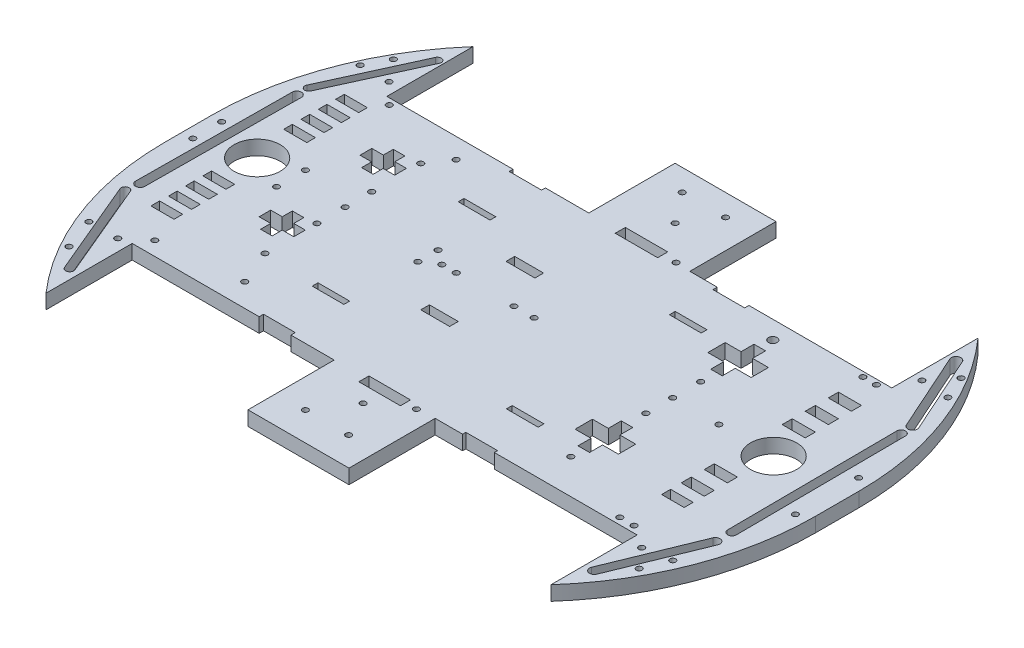
SolidWorks part; units mm, degrees
ref_plane "Front Plane" through (0, 0, 0) normal (0, 0, 1) x (1, 0, 0)
ref_plane "Top Plane" through (0, 0, 0) normal (0, 1, 0) x (1, 0, 0)
ref_plane "Right Plane" through (0, 0, 0) normal (1, 0, 0) x (0, 0, -1)
sketch "Sketch1" plane through (0, 0, 0) normal (0, 1, 0) x (1, 0, 0)
  line L1 (50.2895, -119.8741) -> (-174.7105, -119.8741)
  line L2 (50.2895, -119.8741) -> (50.2895, 28.1259)
  line L3 (50.2895, 28.1259) -> (-174.7105, 28.1259)
  line L4 (-174.7105, -119.8741) -> (-174.7105, 28.1259)
  line L5 (50.2895, -119.8741) -> (-174.7105, 28.1259) construction
  line L6 (50.2895, 28.1259) -> (-174.7105, -119.8741) construction
  point P0 (-62.2105, -45.8741)
extrude "Boss-Extrude1" add sketch "Sketch1" along normal blind 5
sketch "Sketch2" plane through (0, 5, 0) normal (0, 1, 0) x (1, 0, 0)
  line L1 (-150, 28.25) -> (-80, 28.25)
  line L2 (-150, 28.25) -> (-150, -1.75)
  line L3 (-150, -1.75) -> (-80, -1.75)
  line L4 (-80, 28.25) -> (-80, -1.75)
  line L5 (-150, 28.25) -> (-80, -1.75) construction
  line L6 (-150, -1.75) -> (-80, 28.25) construction
  line L7 (-45, 28.25) -> (25, 28.25)
  line L8 (-45, 28.25) -> (-45, -1.75)
  line L9 (-45, -1.75) -> (25, -1.75)
  line L10 (25, 28.25) -> (25, -1.75)
  line L11 (-45, 28.25) -> (25, -1.75) construction
  line L12 (-45, -1.75) -> (25, 28.25) construction
  line L13 (-150, -90) -> (-80, -90)
  line L14 (-150, -90) -> (-150, -120)
  line L15 (-150, -120) -> (-80, -120)
  line L16 (-80, -90) -> (-80, -120)
  line L17 (-150, -90) -> (-80, -120) construction
  line L18 (-150, -120) -> (-80, -90) construction
  line L19 (-45, -90) -> (25, -90)
  line L20 (-45, -90) -> (-45, -120)
  line L21 (-45, -120) -> (25, -120)
  line L22 (25, -90) -> (25, -120)
  line L23 (-45, -90) -> (25, -120) construction
  line L24 (-45, -120) -> (25, -90) construction
  point P0 (-115, 13.25)
  point P5 (-10, 13.25)
  point P10 (-10, -105)
  point P11 (-115, -105)
  point P20 (0, 0)
  point P21 (0, 0)
  point P22 (0, 0)
  point P23 (0, 0)
  point P24 (0, 0)
  point P25 (0, 0)
  point P26 (0, 0)
  point P27 (0, 0)
  point P28 (0, 0)
  point P29 (0, 0)
  point P30 (0, 0)
  point P31 (0, 0)
  point P32 (0, 0)
extrude "Cut-Extrude4" cut sketch "Sketch2" against normal blind 5
fillet "Fillet3" radius 100 1 edges at (50.2895, 2.5, -28.1259)
fillet "Fillet4" radius 100 1 edges at (50.2895, 2.5, 119.8741)
fillet "Fillet5" radius 100 1 edges at (-174.7105, 2.5, 119.8741)
fillet "Fillet6" radius 100 1 edges at (-174.7105, 2.5, -28.1259)
sketch "Sketch3" plane through (0, 5, 0) normal (0, 1, 0) x (1, 0, 0)
  line L0 (40.2781, -13.7848) -> (40.6645, -72.7835) construction
  line L1 (41.7887, -13.7749) -> (42.1752, -72.7736)
  line L2 (38.7674, -13.7947) -> (39.1539, -72.7934)
  line L3 (40.4626, -78.3743) -> (28.2879, -108.1748) construction
  line L4 (41.9597, -78.986) -> (29.785, -108.7865)
  line L5 (38.9654, -77.7627) -> (26.7907, -107.5632)
  line L6 (40.1409, -9.6854) -> (27.8591, 17.6854) construction
  line L7 (38.6468, -10.3558) -> (26.365, 17.0149)
  line L8 (41.635, -9.0149) -> (29.3532, 18.3558)
  arc A0 (41.7887, -13.7749) -> (38.7674, -13.7947) centre (40.2781, -13.7848) ccw
  arc A1 (39.1539, -72.7934) -> (42.1752, -72.7736) centre (40.6645, -72.7835) ccw
  arc A2 (41.9597, -78.986) -> (38.9654, -77.7627) centre (40.4626, -78.3743) ccw
  arc A3 (26.7907, -107.5632) -> (29.785, -108.7865) centre (28.2879, -108.1748) ccw
  arc A4 (38.6468, -10.3558) -> (41.635, -9.0149) centre (40.1409, -9.6854) ccw
  arc A5 (29.3532, 18.3558) -> (26.365, 17.0149) centre (27.8591, 17.6854) ccw
  point P2 (40.4713, -43.2842)
  point P7 (34.3752, -93.2746)
  point P14 (34, 4)
extrude "Cut-Extrude5" cut sketch "Sketch3" against normal blind 5
sketch "Sketch4" plane through (0, 5, 0) normal (0, 1, 0) x (1, 0, 0)
  circle A0 centre (46.243, -34.4925) radius 1
  circle A1 centre (46.243, -56.4082) radius 1
extrude "Cut-Extrude6" cut sketch "Sketch4" against normal blind 5
sketch "Sketch5" plane through (0, 5, 0) normal (0, 1, 0) x (1, 0, 0)
  circle A0 centre (16.7247, -87.7343) radius 1
  circle A1 centre (21.6512, -87.7207) radius 1
  circle A2 centre (29.6052, -93.0384) radius 1
  circle A3 centre (35.4425, -99.7319) radius 1
  circle A4 centre (38.8294, -91.479) radius 1
  circle A5 centre (27.9671, 5.7106) radius 1
  circle A6 centre (34.048, 13.2015) radius 1
  circle A7 centre (37.5731, 5.0937) radius 1
  circle A8 centre (16.7037, -3.4746) radius 1
  circle A9 centre (21.3826, -3.4853) radius 1
  point P20 (0, 0)
  point P21 (16.7247, -87.7343)
  point P22 (0, 0)
  point P23 (0, 0)
  point P24 (0, 0)
  point P25 (0, 0)
  point P26 (35.4425, -99.7319)
  point P27 (0, 0)
  point P28 (29.6052, -93.0384)
extrude "Cut-Extrude7" cut sketch "Sketch5" against normal blind 5
sketch "Sketch6" plane through (0, 5, 0) normal (0, 1, 0) x (1, 0, 0)
  line L0 (-166.5243, -70.7082) -> (-166.0912, -16.8551) construction
  line L1 (17, -12.25) -> (25, -12.25)
  line L2 (17, -12.25) -> (17, -15.75)
  line L3 (17, -15.75) -> (25, -15.75)
  line L4 (25, -12.25) -> (25, -15.75)
  line L5 (17, -12.25) -> (25, -15.75) construction
  line L6 (17, -15.75) -> (25, -12.25) construction
  line L7 (17, -20.25) -> (25, -20.25)
  line L8 (17, -20.25) -> (17, -23.75)
  line L9 (17, -23.75) -> (25, -23.75)
  line L10 (25, -20.25) -> (25, -23.75)
  line L11 (17, -20.25) -> (25, -23.75) construction
  line L12 (17, -23.75) -> (25, -20.25) construction
  line L13 (25, -31.75) -> (17, -31.75)
  line L14 (25, -31.75) -> (25, -28.25)
  line L15 (25, -28.25) -> (17, -28.25)
  line L16 (17, -31.75) -> (17, -28.25)
  line L17 (25, -31.75) -> (17, -28.25) construction
  line L18 (25, -28.25) -> (17, -31.75) construction
  line L19 (25, -74.75) -> (17, -74.75)
  line L20 (25, -74.75) -> (25, -71.25)
  line L21 (25, -71.25) -> (17, -71.25)
  line L22 (17, -74.75) -> (17, -71.25)
  line L23 (25, -74.75) -> (17, -71.25) construction
  line L24 (25, -71.25) -> (17, -74.75) construction
  line L25 (25, -66.75) -> (17, -66.75)
  line L26 (25, -66.75) -> (25, -63.25)
  line L27 (25, -63.25) -> (17, -63.25)
  line L28 (17, -66.75) -> (17, -63.25)
  line L29 (25, -66.75) -> (17, -63.25) construction
  line L30 (25, -63.25) -> (17, -66.75) construction
  line L31 (25, -58.75) -> (17, -58.75)
  line L32 (25, -58.75) -> (25, -55.25)
  line L33 (25, -55.25) -> (17, -55.25)
  line L34 (17, -58.75) -> (17, -55.25)
  line L35 (25, -58.75) -> (17, -55.25) construction
  line L36 (25, -55.25) -> (17, -58.75) construction
  line L37 (-17.5, -17) -> (-2.5, -17)
  line L38 (-17.5, -17) -> (-17.5, -23)
  line L39 (-17.5, -23) -> (-2.5, -23)
  line L40 (-2.5, -17) -> (-2.5, -23)
  line L41 (-17.5, -17) -> (-2.5, -23) construction
  line L42 (-17.5, -23) -> (-2.5, -17) construction
  line L43 (-12, -12.5) -> (-8, -12.5)
  line L44 (-12, -12.5) -> (-12, -27.5)
  line L45 (-12, -27.5) -> (-8, -27.5)
  line L46 (-8, -12.5) -> (-8, -27.5)
  line L47 (-12, -12.5) -> (-8, -27.5) construction
  line L48 (-12, -27.5) -> (-8, -12.5) construction
  line L49 (-2.5, -63) -> (-17.5, -63)
  line L50 (-2.5, -63) -> (-2.5, -69)
  line L51 (-2.5, -69) -> (-17.5, -69)
  line L52 (-17.5, -63) -> (-17.5, -69)
  line L53 (-2.5, -63) -> (-17.5, -69) construction
  line L54 (-2.5, -69) -> (-17.5, -63) construction
  line L59 (-12, -58.5) -> (-8, -58.5)
  line L60 (-12, -58.5) -> (-12, -73.5)
  line L61 (-12, -73.5) -> (-8, -73.5)
  line L62 (-8, -58.5) -> (-8, -73.5)
  line L63 (-12, -58.5) -> (-8, -73.5) construction
  line L64 (-12, -73.5) -> (-8, -58.5) construction
  line L65 (-35.5, -72.8105) -> (-24.5, -72.8105)
  line L66 (-35.5, -72.8105) -> (-35.5, -74.8105)
  line L67 (-35.5, -74.8105) -> (-24.5, -74.8105)
  line L68 (-24.5, -72.8105) -> (-24.5, -74.8105)
  line L69 (-35.5, -72.8105) -> (-24.5, -74.8105) construction
  line L70 (-35.5, -74.8105) -> (-24.5, -72.8105) construction
  line L71 (-35.5, -16.3105) -> (-24.5, -16.3105)
  line L72 (-35.5, -16.3105) -> (-35.5, -18.3105)
  line L73 (-35.5, -18.3105) -> (-24.5, -18.3105)
  line L74 (-24.5, -16.3105) -> (-24.5, -18.3105)
  line L75 (-35.5, -16.3105) -> (-24.5, -18.3105) construction
  line L76 (-35.5, -18.3105) -> (-24.5, -16.3105) construction
  line L77 (-35.5, -93.3727) -> (-24.5, -93.3727)
  line L78 (-35.5, -93.3727) -> (-35.5, -88.8727)
  line L79 (-35.5, -88.8727) -> (-24.5, -88.8727)
  line L80 (-24.5, -93.3727) -> (-24.5, -88.8727)
  line L81 (-35.5, -93.3727) -> (-24.5, -88.8727) construction
  line L82 (-35.5, -88.8727) -> (-24.5, -93.3727) construction
  line L83 (-35.5, 2.5195) -> (-24.5, 2.5195)
  line L84 (-35.5, 2.5195) -> (-35.5, -3.2305)
  line L85 (-35.5, -3.2305) -> (-24.5, -3.2305)
  line L86 (-24.5, 2.5195) -> (-24.5, -3.2305)
  line L87 (-35.5, 2.5195) -> (-24.5, -3.2305) construction
  line L88 (-35.5, -3.2305) -> (-24.5, 2.5195) construction
  line L89 (-69.2029, -88.75) -> (-54.7971, -88.75)
  line L90 (-69.2029, -88.75) -> (-69.2029, -92.25)
  line L91 (-69.2029, -92.25) -> (-54.7971, -92.25)
  line L92 (-54.7971, -88.75) -> (-54.7971, -92.25)
  line L93 (-69.2029, -88.75) -> (-54.7971, -92.25) construction
  line L94 (-69.2029, -92.25) -> (-54.7971, -88.75) construction
  line L95 (-69.3499, 0.25) -> (-54.6501, 0.25)
  line L96 (-69.3499, 0.25) -> (-69.3499, -3.25)
  line L97 (-69.3499, -3.25) -> (-54.6501, -3.25)
  line L98 (-54.6501, 0.25) -> (-54.6501, -3.25)
  line L99 (-69.3499, 0.25) -> (-54.6501, -3.25) construction
  line L100 (-69.3499, -3.25) -> (-54.6501, 0.25) construction
  line L105 (-79.8242, -27.6088) -> (-69.8242, -27.6088)
  line L106 (-79.8242, -27.6088) -> (-79.8242, -30.6088)
  line L107 (-79.8242, -30.6088) -> (-69.8242, -30.6088)
  line L108 (-69.8242, -27.6088) -> (-69.8242, -30.6088)
  line L109 (-79.8242, -27.6088) -> (-69.8242, -30.6088) construction
  line L110 (-79.8242, -30.6088) -> (-69.8242, -27.6088) construction
  line L115 (-80.0706, -56.9279) -> (-70.0706, -56.9279)
  line L116 (-80.0706, -56.9279) -> (-80.0706, -59.9279)
  line L117 (-80.0706, -59.9279) -> (-70.0706, -59.9279)
  line L118 (-70.0706, -56.9279) -> (-70.0706, -59.9279)
  line L119 (-80.0706, -56.9279) -> (-70.0706, -59.9279) construction
  line L120 (-80.0706, -59.9279) -> (-70.0706, -56.9279) construction
  line L125 (-106, -69.6259) -> (-95, -69.6259)
  line L126 (-106, -69.6259) -> (-106, -71.6259)
  line L127 (-106, -71.6259) -> (-95, -71.6259)
  line L128 (-95, -69.6259) -> (-95, -71.6259)
  line L129 (-106, -69.6259) -> (-95, -71.6259) construction
  line L130 (-106, -71.6259) -> (-95, -69.6259) construction
  line L135 (-106, -19) -> (-95, -19)
  line L136 (-106, -19) -> (-106, -21)
  line L137 (-106, -21) -> (-95, -21)
  line L138 (-95, -19) -> (-95, -21)
  line L139 (-106, -19) -> (-95, -21) construction
  line L140 (-106, -21) -> (-95, -19) construction
  line L141 (-106, 2.7025) -> (-95, 2.7025)
  line L142 (-106, 2.7025) -> (-106, -2.6808)
  line L143 (-106, -2.6808) -> (-95, -2.6808)
  line L144 (-95, 2.7025) -> (-95, -2.6808)
  line L145 (-106, 2.7025) -> (-95, -2.6808) construction
  line L146 (-106, -2.6808) -> (-95, 2.7025) construction
  line L147 (-95, -99.2647) -> (-106, -99.2647)
  line L148 (-95, -99.2647) -> (-95, -88.4979)
  line L149 (-95, -88.4979) -> (-106, -88.4979)
  line L150 (-106, -99.2647) -> (-106, -88.4979)
  line L151 (-95, -99.2647) -> (-106, -88.4979) construction
  line L152 (-95, -88.4979) -> (-106, -99.2647) construction
  line L153 (-168.1147, -70.6954) -> (-167.6815, -16.8423)
  line L154 (-164.9339, -70.721) -> (-164.5008, -16.8679)
  line L155 (-167.2462, -75.1839) -> (-153.2669, -108.3856) construction
  line L156 (-165.9733, -74.648) -> (-151.994, -107.8496)
  line L157 (-168.5191, -75.7198) -> (-154.5398, -108.9215)
  line L158 (-166.0364, -12.7868) -> (-152.0599, 17.8339) construction
  line L159 (-167.2621, -12.2274) -> (-153.2856, 18.3934)
  line L160 (-164.8108, -13.3463) -> (-150.8343, 17.2745)
  line L162 (-158, -26.5) -> (-150, -26.5)
  line L163 (-158, -26.5) -> (-158, -29.5)
  line L164 (-158, -29.5) -> (-150, -29.5)
  line L165 (-150, -26.5) -> (-150, -29.5)
  line L166 (-158, -26.5) -> (-150, -29.5) construction
  line L167 (-158, -29.5) -> (-150, -26.5) construction
  line L168 (-158, -20.5) -> (-150, -20.5)
  line L169 (-158, -20.5) -> (-158, -23.5)
  line L170 (-158, -23.5) -> (-150, -23.5)
  line L171 (-150, -20.5) -> (-150, -23.5)
  line L172 (-158, -20.5) -> (-150, -23.5) construction
  line L173 (-158, -23.5) -> (-150, -20.5) construction
  line L174 (-158, -14.5) -> (-150, -14.5)
  line L175 (-158, -14.5) -> (-158, -17.5)
  line L176 (-158, -17.5) -> (-150, -17.5)
  line L177 (-150, -14.5) -> (-150, -17.5)
  line L178 (-158, -14.5) -> (-150, -17.5) construction
  line L179 (-158, -17.5) -> (-150, -14.5) construction
  line L180 (-158, -8.5) -> (-150, -8.5)
  line L181 (-158, -8.5) -> (-158, -11.5)
  line L182 (-158, -11.5) -> (-150, -11.5)
  line L183 (-150, -8.5) -> (-150, -11.5)
  line L184 (-158, -8.5) -> (-150, -11.5) construction
  line L185 (-158, -11.5) -> (-150, -8.5) construction
  line L186 (-158, -54.5) -> (-150, -54.5)
  line L187 (-158, -54.5) -> (-158, -57.5)
  line L188 (-158, -57.5) -> (-150, -57.5)
  line L189 (-150, -54.5) -> (-150, -57.5)
  line L190 (-158, -54.5) -> (-150, -57.5) construction
  line L191 (-158, -57.5) -> (-150, -54.5) construction
  line L192 (-158, -60.5) -> (-150, -60.5)
  line L193 (-158, -60.5) -> (-158, -63.5)
  line L194 (-158, -63.5) -> (-150, -63.5)
  line L195 (-150, -60.5) -> (-150, -63.5)
  line L196 (-158, -60.5) -> (-150, -63.5) construction
  line L197 (-158, -63.5) -> (-150, -60.5) construction
  line L202 (-149.9239, -69.5) -> (-157.9239, -69.5)
  line L203 (-149.9239, -69.5) -> (-149.9239, -66.5)
  line L204 (-149.9239, -66.5) -> (-157.9239, -66.5)
  line L205 (-157.9239, -69.5) -> (-157.9239, -66.5)
  line L206 (-149.9239, -69.5) -> (-157.9239, -66.5) construction
  line L207 (-149.9239, -66.5) -> (-157.9239, -69.5) construction
  line L208 (-150, -75.5) -> (-158, -75.5)
  line L209 (-150, -75.5) -> (-150, -72.5)
  line L210 (-150, -72.5) -> (-158, -72.5)
  line L211 (-158, -75.5) -> (-158, -72.5)
  line L212 (-150, -75.5) -> (-158, -72.5) construction
  line L213 (-150, -72.5) -> (-158, -75.5) construction
  line L218 (-137, -19.9584) -> (-125, -19.9584)
  line L219 (-137, -19.9584) -> (-137, -24.0416)
  line L220 (-137, -24.0416) -> (-125, -24.0416)
  line L221 (-125, -19.9584) -> (-125, -24.0416)
  line L222 (-137, -19.9584) -> (-125, -24.0416) construction
  line L223 (-137, -24.0416) -> (-125, -19.9584) construction
  line L224 (-133, -16.5) -> (-129, -16.5)
  line L225 (-133, -16.5) -> (-133, -27.5)
  line L226 (-133, -27.5) -> (-129, -27.5)
  line L227 (-129, -16.5) -> (-129, -27.5)
  line L228 (-133, -16.5) -> (-129, -27.5) construction
  line L229 (-133, -27.5) -> (-129, -16.5) construction
  line L230 (-136, -56) -> (-124, -56)
  line L231 (-136, -56) -> (-136, -60)
  line L232 (-136, -60) -> (-124, -60)
  line L233 (-124, -56) -> (-124, -60)
  line L234 (-136, -56) -> (-124, -60) construction
  line L235 (-136, -60) -> (-124, -56) construction
  line L236 (-132, -52.5) -> (-128, -52.5)
  line L237 (-132, -52.5) -> (-132, -63.5)
  line L238 (-132, -63.5) -> (-128, -63.5)
  line L239 (-128, -52.5) -> (-128, -63.5)
  line L240 (-132, -52.5) -> (-128, -63.5) construction
  line L241 (-132, -63.5) -> (-128, -52.5) construction
  circle A0 centre (25, -42.7) radius 8
  circle A2 centre (6, -42.7) radius 1
  circle A3 centre (-10, -42.7) radius 1
  circle A4 centre (-10, -33) radius 1
  circle A5 centre (-10, -52) radius 1
  circle A7 centre (-10, -8) radius 1.5
  circle A8 centre (-10, -78) radius 1
  circle A9 centre (-58, -42.7) radius 1
  circle A10 centre (-65, -42.7) radius 1
  circle A11 centre (-62, -97.9843) radius 1
  circle A12 centre (-70, -110) radius 1
  circle A13 centre (-55, -110) radius 1
  circle A14 centre (-62, 10.1723) radius 1
  circle A15 centre (-70, 20.6085) radius 1
  circle A16 centre (-55, 20.6085) radius 1
  circle A17 centre (-50, -1.5) radius 1
  circle A18 centre (-51.0241, -90.5) radius 1
  circle A19 centre (-85, -42.7) radius 1
  circle A20 centre (-90, -42.7) radius 1
  circle A22 centre (-95, -39) radius 1
  circle A23 centre (-95, -46) radius 1
  circle A24 centre (-124, -33) radius 1
  circle A25 centre (-124, -42.2) radius 1
  circle A26 centre (-124, -52) radius 1
  circle A27 centre (-124, -70) radius 1
  circle A28 centre (-119, -82) radius 1
  circle A29 centre (-124, -16) radius 1
  circle A30 centre (-119, -8.7433) radius 1
  circle A31 centre (-142, -38) radius 1
  circle A32 centre (-142, -48) radius 1
  circle A33 centre (-147, -3.922) radius 1
  circle A34 centre (-147, -85.1755) radius 1
  circle A35 centre (-154, 3) radius 1
  circle A36 centre (-160, 10.5) radius 1
  circle A37 centre (-164, 3) radius 1
  circle A38 centre (-171, -38) radius 1
  circle A40 centre (-171, -48) radius 1
  circle A41 centre (-164, -91) radius 1
  circle A42 centre (-160, -101.9083) radius 1
  circle A43 centre (-154, -91) radius 1
  arc A44 (-168.1147, -70.6954) -> (-164.9339, -70.721) centre (-166.5243, -70.7082) ccw
  arc A45 (-164.5008, -16.8679) -> (-167.6815, -16.8423) centre (-166.0912, -16.8551) ccw
  arc A46 (-165.9733, -74.648) -> (-168.5191, -75.7198) centre (-167.2462, -75.1839) ccw
  arc A47 (-154.5398, -108.9215) -> (-151.994, -107.8496) centre (-153.2669, -108.3856) ccw
  arc A48 (-167.2621, -12.2274) -> (-164.8108, -13.3463) centre (-166.0364, -12.7868) ccw
  arc A49 (-150.8343, 17.2745) -> (-153.2856, 18.3934) centre (-152.0599, 17.8339) ccw
  circle A50 centre (-154, -42.7) radius 8
  point P0 (21, -14)
  point P5 (21, -22)
  point P10 (21, -30)
  point P15 (21, -73)
  point P20 (21, -65)
  point P25 (21, -57)
  point P34 (-10, -20)
  point P40 (-10, -20)
  point P48 (-10, -66)
  point P55 (-10, -66)
  point P62 (-30, -17.3105)
  point P67 (-30, -91.1227)
  point P72 (-30, -0.3555)
  point P77 (-30, -73.8105)
  point P90 (-62, -1.5)
  point P96 (-62, -90.5)
  point P120 (-74.8242, -29.1088)
  point P125 (-75.0706, -58.4279)
  point P130 (-100.5, -70.6259)
  point P135 (-100.5, -20)
  point P140 (-100.5, -93.8813)
  point P164 (-100.5, 0.0109)
  point P182 (-166.3077, -43.7816)
  point P195 (-160.2566, -91.7847)
  point P202 (-159.0482, 2.5235)
  point P211 (-154, -22)
  point P216 (-154, -16)
  point P218 (-154, -28)
  point P226 (-154, -10)
  point P231 (-154, -56)
  point P236 (-154, -62)
  point P241 (-153.9239, -68)
  point P248 (-154, -74)
  point P253 (-131, -22)
  point P258 (-131, -22)
  point P263 (-130, -58)
  point P268 (-130, -58)
  point P273 (0, 0)
  point P274 (0, 0)
  point P275 (0, 0)
  point P276 (0, 0)
  point P277 (0, 0)
  point P278 (0, 0)
  point P279 (0, 0)
  point P280 (0, 0)
  point P281 (0, 0)
  point P282 (0, 0)
  point P283 (0, 0)
  point P284 (0, 0)
  point P285 (0, 0)
  point P286 (0, 0)
  point P287 (0, 0)
  point P288 (0, 0)
  point P289 (0, 0)
  point P290 (0, 0)
  point P291 (0, 0)
  point P292 (0, 0)
  point P293 (0, 0)
  point P294 (0, 0)
  point P295 (0, 0)
  point P296 (0, 0)
  point P297 (0, 0)
  point P298 (0, 0)
  point P299 (0, 0)
  point P300 (0, 0)
  point P301 (0, 0)
  point P302 (0, 0)
  point P303 (0, 0)
  point P304 (0, 0)
  point P305 (0, 0)
  point P306 (0, 0)
  point P307 (0, 0)
  point P308 (0, 0)
  point P309 (0, 0)
  point P310 (0, 0)
  point P311 (0, 0)
  point P312 (0, 0)
  point P313 (0, 0)
  point P314 (0, 0)
  point P315 (0, 0)
  point P316 (0, 0)
  point P317 (0, 0)
  point P318 (0, 0)
  point P319 (0, 0)
  point P320 (0, 0)
  point P321 (0, 0)
  point P322 (0, 0)
  point P323 (0, 0)
  point P324 (0, 0)
  point P325 (0, 0)
  point P326 (0, 0)
  point P327 (0, 0)
  point P328 (0, 0)
  line M195 (-150, -90) -> (-80, -90)
  line M209 (-80, -1.75) -> (-150, -1.75)
extrude "Cut-Extrude8" cut sketch "Sketch6" against normal blind 5 contours L144 L141 L142 M209 | A50 | L189 L186 L187 L188 | L195 L192 L193 L194 | L205 L202 L203 L204 | L211 L208 L209 L210 | L237 L230 L231 L232 | L239 L236 L237 L230 | L239 L230 L237 L232 | L230 L239 L232 L233 | L239 L232 L237 L238 | A26 | L150 L148 L149 M195 | L128 L125 L126 L127 | L138 L135 L136 L137 | L118 L115 L116 L117 | L98 L95 L96 L97 | L74 L71 L72 L73 | L44 L37 L38 L39 | L46 L43 L44 L37 | L37 L46 L39 L40 | L46 L37 L44 L39 | L46 L39 L44 L45 | A7 | A0 | L16 L13 L14 L15 | L10 L7 L8 L9 | L4 L1 L2 L3 | L34 L31 L32 L33 | L28 L25 L26 L27 | L62 L59 L60 L49 | L49 L62 L51 L50 | L60 L49 L52 L51 | L62 L49 L60 L51 | L62 L51 L60 L61 | A8 | L68 L65 L66 L67 | L92 L89 L90 L91 | L108 L107 L106 L105 | L224 L227 L226 L225 | L159 A49 L160 A48 | A37 | A36 | A38 | L165 L164 L163 L162 | L171 L170 L169 L168 | L177 L176 L175 L174 | L183 L182 L181 L180 | A35 | A33 | L219 L220 L221 L218 | L154 A45 L153 A44 | A40 | L156 A47 L157 A46 | A41 | A42 | A34 | A43 | A27 | A28 | A30 | A29 | A31 | A32 | A25 | A24 | A22 | A23 | A20 | A19 | A10 | A9 | A17 | A15 | A16 | A14 | L85 L86 L83 L84 | A4 | A3 | A5 | A2 | A11 | A12 | A13 | A18 | L79 L80 L77 L78 region at (21, 5, 14) region at (21, 5, 22) region at (21, 5, 30) region at (21, 5, 65) region at (21, 5, 57) region at (-14.75, 5, 20) region at (-10, 5, 14.75) region at (-10, 5, 20) region at (-5.25, 5, 20) region at (-10, 5, 25.25) region at (-5.25, 5, 66) region at (-10, 5, 66) region at (-10, 5, 60.75) region at (-14.75, 5, 66) region at (-10, 5, 71.25) region at (-30, 5, 73.8105) region at (-30, 5, 17.3105) region at (-62, 5, 90.5) region at (-62, 5, 1.5) region at (-75.0706, 5, 58.4279) region at (-100.5, 5, 70.6259) region at (-100.5, 5, 20) region at (-100.5, 5, -0.4763) region at (-100.5, 5, 89.249) region at (-154, 5, 56) region at (-154, 5, 62) region at (-153.9239, 5, 68) region at (-154, 5, 74) region at (-134, 5, 58) region at (-130, 5, 54.25) region at (-130, 5, 58) region at (-126, 5, 58) region at (-130, 5, 61.75) region at (25, 5, 42.7) region at (-10, 5, 8) region at (-10, 5, 78) region at (-124, 5, 52) region at (-154, 5, 42.7)
sketch "Sketch7" plane through (0, 5, 0) normal (0, 1, 0) x (1, 0, 0)
  line L1 (24.9024, -73.6248) -> (17.0976, -73.6248)
  line L2 (24.9024, -73.6248) -> (24.9024, -70.5029)
  line L3 (24.9024, -70.5029) -> (17.0976, -70.5029)
  line L4 (17.0976, -73.6248) -> (17.0976, -70.5029)
  line L5 (24.9024, -73.6248) -> (17.0976, -70.5029) construction
  line L6 (24.9024, -70.5029) -> (17.0976, -73.6248) construction
  line L11 (-95.0625, 4.6718) -> (-106.2552, 4.6718)
  line L12 (-95.0625, 4.6718) -> (-95.0625, -3.077)
  line L13 (-95.0625, -3.077) -> (-106.2552, -3.077)
  line L14 (-106.2552, 4.6718) -> (-106.2552, -3.077)
  line L15 (-95.0625, 4.6718) -> (-106.2552, -3.077) construction
  line L16 (-95.0625, -3.077) -> (-106.2552, 4.6718) construction
  point P0 (21, -72.0639)
  point P6 (-100.6589, 0.7974)
extrude "Cut-Extrude9" cut sketch "Sketch7" against normal blind 5
